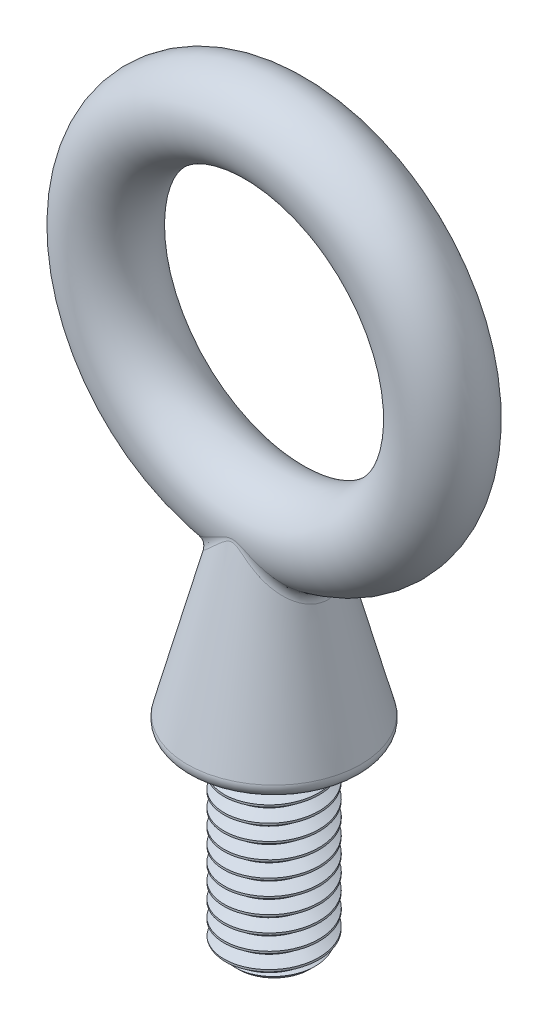
SolidWorks part; units mm, degrees
ref_plane "Front Plane" through (0, 0, 0) normal (0, 0, 1) x (1, 0, 0)
ref_plane "Top Plane" through (0, 0, 0) normal (0, 1, 0) x (1, 0, 0)
ref_plane "Right Plane" through (0, 0, 0) normal (1, 0, 0) x (0, 0, -1)
sketch "Sketch1" plane through (0, 0, 0) normal (0, 0, 1) x (1, 0, 0)
  line L0 (0, -21.0344) -> (0, -54.3719) construction
  line L1 (-4.7625, -54.3719) -> (4.7625, -54.3719) construction
  line L3 (0, -21.0344) -> (0, -12.7) construction
  line L4 (-8.7312, -35.3219) -> (8.7313, -35.3219) construction
  circle A0 centre (0, 0) radius 21.0344 construction
  circle A1 centre (0, 16.8672) radius 4.1672 construction
  circle A2 centre (0, 0) radius 12.7 construction
  point P7 (0, -21.0344)
  point P9 (0, -35.3219)
  point P10 (0, 21.0344)
  point P11 (0, 12.7)
  point P14 (0, -54.3719)
  point P19 (0, -16.8672)
  point P21 (0, -35.3219)
  dimension "A" = 8.3344
  dimension "Eye Dia." = 25.4
  dimension "Overall Lg." = 75.4062
  dimension "Shank Lg." = 19.05
  dimension "OD" = 42.0688
  dimension "Thread Lg." = 19.05
  dimension "Thread OD" = 9.525
  dimension "Shoulder Dia." = 17.4625
  dimension "Thickness" = 14.2875
sketch "Sketch2" plane through (0, 0, 0) normal (0, 1, 0) x (1, 0, 0)
  circle A0 centre (0, 0) radius 4.7625
extrude "Boss-Extrude1" add sketch "Sketch2" against normal up to vertex (54.3719 mm away) from vertex at -35.3219 starting at point (0, -35.3219, 0)
sketch "Sketch3" plane through (0, -54.3719, 0) normal (0, -1, 0) x (1, 0, 0)
  circle A1 centre (0, 0) radius 4.7625
  circle A2 centre (0, 0) radius 4.7625
  point P0 (4.7625, 0)
  point P1 (0, -4.7625)
  dimension "D1" = 0
curve "Helix/Spiral1" pitch 1.5875 height 20.6375 turns 13 parameters "Pitch"=1.5875
sketch "Sketch4" plane through (0, 0, 0) normal (0, 0, 1) x (1, 0, 0)
  line L0 (4.9344, -54.2727) -> (4.9344, -55.8602) construction
  line L1 (4.9344, -55.8602) -> (3.5595, -55.0664) construction
  line L2 (3.5595, -55.0664) -> (4.9344, -54.2727) construction
  line L3 (3.7314, -54.9672) -> (3.7314, -55.1656) construction
  line L4 (4.7625, -54.3719) -> (4.7625, -55.7609) construction
  line L5 (3.5595, -55.0664) -> (3.7314, -55.0664) construction
  line L6 (4.7625, -55.0664) -> (4.9344, -55.0664) construction
  line L7 (4.8484, -54.3223) -> (3.7314, -54.9672)
  line L8 (3.7314, -54.9672) -> (3.7314, -55.1656)
  line L9 (3.7314, -55.1656) -> (4.8484, -55.8105)
  line L10 (4.8484, -55.8105) -> (4.8484, -54.3223)
  point P13 (4.8484, -55.0664)
  dimension "D1" = 1.5875
  dimension "D2" = 0.1984
sweep "Cut-Sweep1" cut profiles "Sketch4" path "Helix/Spiral1" align with end faces yes
sketch "Sketch5" plane through (0, -54.3719, 0) normal (0, -1, 0) x (1, 0, 0)
  circle A0 centre (0, 0) radius 3.5595
extrude "Cut-Extrude1" cut sketch "Sketch5" against normal through all draft 45 flip side to cut
sketch "Sketch6" plane through (0, 0, 0) normal (1, 0, 0) x (0, 0, -1)
  circle A0 centre (0, 16.8672) radius 4.1672
ref_axis "Axis1" through (0, 0, -7.6398) along (0, 0, 1)
revolve "Revolve1" add sketch "Sketch6" angle 360 about axis through (0, 0, -7.6398) along (0, 0, 1)
sketch "Sketch7" plane through (0, -35.3219, 0) normal (0, 1, 0) x (1, 0, 0)
  circle A1 centre (0, 0) radius 4.7625
  circle A2 centre (0, 0) radius 4.7625
  dimension "D1" = 0
extrude "Boss-Extrude2" [suppressed] add sketch "Sketch7" along normal up to vertex (9.525 mm away)
sketch "Sketch8" plane through (0, 0, 0) normal (0, 0, 1) x (1, 0, 0)
  line L0 (0, -35.3219) -> (0, -16.8672)
  line L1 (0, -16.8672) -> (-4.1672, -16.8672)
  line L2 (-7.6895, -35.3219) -> (-8.7312, -35.3219) construction
  line L3 (-8.7312, -35.3219) -> (-8.7312, -34.2801) construction
  line L5 (-8.7312, -35.3219) -> (8.7313, -35.3219) construction
  line L6 (-8.6967, -34.014) -> (-4.1672, -16.8672)
  line L9 (-7.6895, -35.3219) -> (0, -35.3219)
  arc A0 (-8.6967, -34.014) -> (-7.6895, -35.3219) centre (-7.6895, -34.2801) ccw
  circle A1 centre (0, -16.8672) radius 4.1672 construction
  dimension "D1" = 1.0418
revolve "Revolve2" add sketch "Sketch8" angle 360 about L0
fillet "Fillet1" radius 1.0418 1 edges at (4.338, -19.8199, 2.3783)
sketch "SketchX" plane through (0, 0, 0) normal (1, 0, 0) x (0, 0, -1)
  line L0 (4.7625, -54.3719) -> (4.7625, -47.625) construction
  dimension "D1" = 6.7469
equation "\"D3@Helix/Spiral1\" = \"Pitch@Helix/Spiral1\" + \"Thread Lg.@Sketch1\""
equation "\"D1@Sketch4\" = \"Pitch@Helix/Spiral1\""
equation "\"D2@Sketch4\" = \"D1@Sketch4\" / 8"
equation "\"D1@Sketch8\" = \"A@Sketch1\" / 8"
equation "\"D1@Fillet1\" = \"A@Sketch1\" / 8"
equation "\"D1@SketchX\" = 1/4 + \"Pitch@Helix/Spiral1\" /  4"
